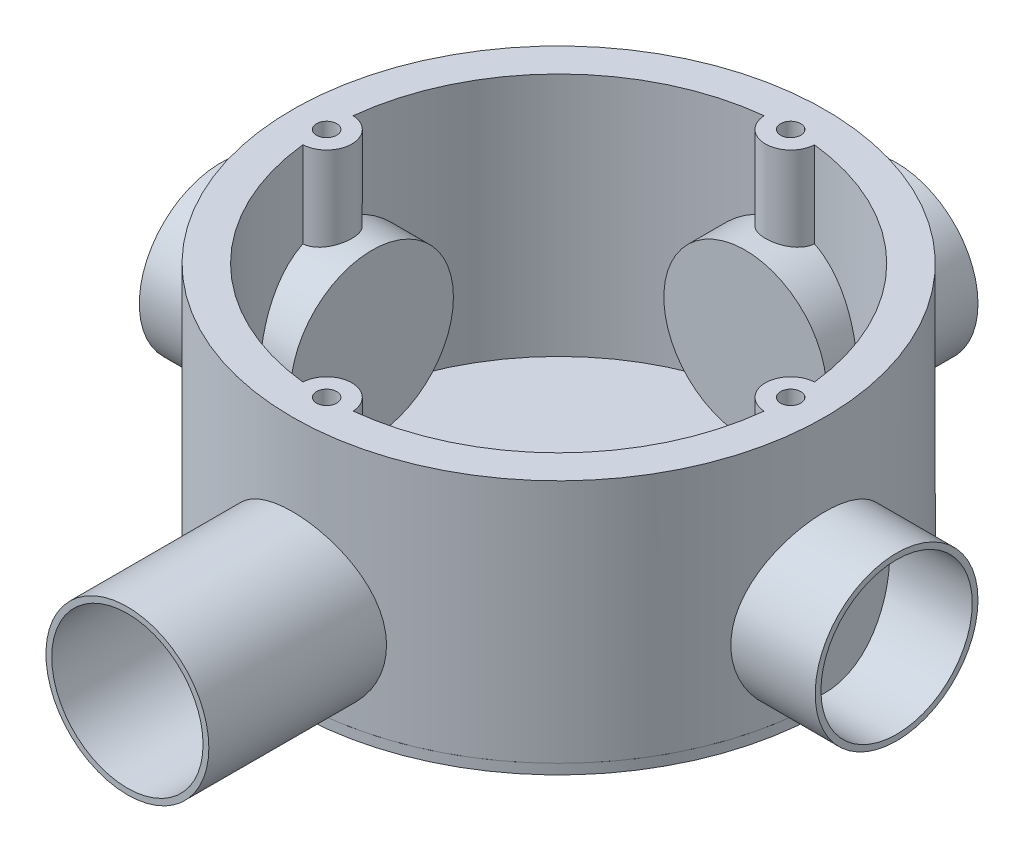
SolidWorks part; units mm, degrees
ref_plane "Plan de face" through (0, 0, 0) normal (0, 0, 1) x (1, 0, 0)
ref_plane "Plan de dessus" through (0, 0, 0) normal (0, 1, 0) x (1, 0, 0)
ref_plane "Plan de droite" through (0, 0, 0) normal (1, 0, 0) x (0, 0, -1)
sketch "Esquisse1" plane through (0, 0, 0) normal (0, 1, 0) x (1, 0, 0)
  line L0 (0, 0) -> (0, 52.8) construction
  line L1 (0, 52.8) -> (0, -52.8) construction
  line L2 (0, -52.8) -> (52.8, 0) construction
  line L3 (52.8, 0) -> (-52.8, 0) construction
  line L4 (0, 46) -> (0, 52.8) construction
  line L5 (0, 46) -> (0, 49.4) construction
  arc A0 (-45.7283, -4.9926) -> (-4.9926, -45.7283) centre (0, 0) ccw
  circle A1 centre (0, 0) radius 52.8
  arc A2 (-4.9926, 45.7283) -> (4.9926, 45.7283) centre (0, 46) ccw
  arc A4 (4.9926, -45.7283) -> (-4.9926, -45.7283) centre (0, -46) ccw
  arc A5 (-45.7283, -4.9926) -> (-45.7283, 4.9926) centre (-46, 0) ccw
  circle A6 centre (46, 0) radius 2
  circle A7 centre (0, -46) radius 2
  circle A8 centre (-46, 0) radius 2
  circle A9 centre (0, 46) radius 2
  arc A10 (4.9926, -45.7283) -> (45.7283, -4.9926) centre (0, 0) ccw
  arc A11 (45.7283, 4.9926) -> (4.9926, 45.7283) centre (0, 0) ccw
  arc A12 (45.7283, 4.9926) -> (45.7283, -4.9926) centre (46, 0) ccw
  arc A13 (-4.9926, 45.7283) -> (-45.7283, 4.9926) centre (0, 0) ccw
extrude "Boss.-Extru.1" add sketch "Esquisse1" along normal blind 48.5
sketch "Esquisse2" plane through (0, 0, 0) normal (0, 0, 1) x (1, 0, 0)
  line L0 (0, 48.5) -> (0, 0) construction
  line L1 (52.8, 48.5) -> (-52.8, 48.5) construction
  line L2 (0, 0) -> (0, 16.15) construction
  line L3 (-44, 48.5) -> (-48, 48.5) construction
  circle A0 centre (0, 16.15) radius 16.15
  circle A1 centre (0, 16.15) radius 15
sketch "Esquisse3" plane through (0, 48.5, 0) normal (0, 1, 0) x (1, 0, 0)
  line L0 (0, -46) -> (0, -37) construction
  line L1 (0, -37) -> (-8.1337, -37) construction
ref_plane "Plan1" through (0, 0, 37) normal (0, 0, 1) x (1, 0, 0)
extrude "Boss.-Extru.2" add sketch "Esquisse2" along normal blind 48.5 from surface starting at plane "Plan1"
sketch "Esquisse4" plane through (0, 0, 37) normal (0, 0, -1) x (-1, 0, 0)
  circle A0 centre (0, 16.15) radius 16.15
extrude "Boss.-Extru.3" add sketch "Esquisse4" against normal blind 3
sketch "Esquisse5" plane through (0, 48.5, 0) normal (0, 1, 0) x (1, 0, 0)
  line L0 (46, 0) -> (37, 0) construction
  line L1 (0, 46) -> (0, 37) construction
  line L2 (0, 37) -> (-46, 0) construction
  line L3 (-46, 0) -> (-37, 0) construction
ref_plane "Plan2" through (0, 0, -37) normal (0, 0, 1) x (1, 0, 0)
ref_plane "Plan3" through (-37, 0, 0) normal (1, 0, 0) x (0, 0, -1)
ref_plane "Plan4" through (37, 0, 0) normal (1, 0, 0) x (0, 0, -1)
sketch "Esquisse6" plane through (-37, 0, 0) normal (1, 0, 0) x (0, 0, -1)
  line L0 (0, 0) -> (0, 16.14) construction
  circle A0 centre (0, 16.14) radius 16.14
  circle A1 centre (0, 16.14) radius 15
extrude "Boss.-Extru.4" add sketch "Esquisse6" against normal blind 30
sketch "Esquisse7" plane through (-37, 0, 0) normal (1, 0, 0) x (0, 0, -1)
  circle A0 centre (0, 16.14) radius 16.14
extrude "Boss.-Extru.5" add sketch "Esquisse7" against normal blind 3
sketch "Esquisse8" plane through (0, 0, -37) normal (0, 0, 1) x (1, 0, 0)
  line L0 (0, 0) -> (0, 16.14) construction
  circle A0 centre (0, 16.14) radius 16.14
  circle A1 centre (0, 16.14) radius 15
extrude "Boss.-Extru.6" add sketch "Esquisse8" against normal blind 30
sketch "Esquisse9" plane through (0, 0, -37) normal (0, 0, 1) x (1, 0, 0)
  circle A0 centre (0, 16.14) radius 16.14
extrude "Boss.-Extru.7" add sketch "Esquisse9" against normal blind 3
sketch "Esquisse10" plane through (37, 0, 0) normal (1, 0, 0) x (0, 0, -1)
  line L0 (0, 0) -> (0, 16.14) construction
  circle A0 centre (0, 16.14) radius 16.14
  circle A1 centre (0, 16.14) radius 15
extrude "Boss.-Extru.8" add sketch "Esquisse10" along normal blind 30
sketch "Esquisse11" plane through (37, 0, 0) normal (-1, 0, 0) x (0, 0, 1)
  circle A0 centre (0, 16.14) radius 16.14
extrude "Boss.-Extru.9" add sketch "Esquisse11" against normal blind 3
sketch "Esquisse12" plane through (0, 0, 0) normal (0, -1, 0) x (-1, 0, 0)
  circle A0 centre (0, 0) radius 52.8
extrude "Boss.-Extru.12" add sketch "Esquisse12" along normal blind 2 separate body
sketch "Esquisse13" plane through (0, 0, 0) normal (0, 1, 0) x (1, 0, 0)
  line L0 (16.14, 40.0378) -> (16.14, 31.0446) construction
  line L1 (16.14, 37) -> (16.14, 43.0755) construction
  line L2 (16.14, 31.0446) -> (16.14, 37) construction
  line L3 (-27.775, 37) -> (27.775, 37) construction
  line L4 (16.14, 37) -> (37, 16.14) construction
  line L5 (37, -27.775) -> (37, 27.775) construction
  circle A0 centre (26.57, 26.57) radius 6
  circle A1 centre (26.57, 26.57) radius 3.9541
extrude "Boss.-Extru.13" add sketch "Esquisse13" along normal blind 3.8
sketch "Esquisse14" plane through (0, 0, 0) normal (0, 1, 0) x (1, 0, 0)
  line L0 (-40.0378, -16.14) -> (-37, -16.14) construction
  line L1 (-43.0755, -16.14) -> (-37, -16.14) construction
  line L2 (-37, -27.775) -> (-37, 27.775) construction
  line L3 (-37, -16.14) -> (-16.15, -37) construction
  circle A0 centre (-26.575, -26.57) radius 6
  circle A1 centre (-26.575, -26.57) radius 3
extrude "Boss.-Extru.14" add sketch "Esquisse14" along normal blind 3.8
sketch "Esquisse15" plane through (0, 0, 0) normal (0, 1, 0) x (1, 0, 0)
  circle A0 centre (0, 0) radius 7.5
extrude "Boss.-Extru.15" add sketch "Esquisse15" along normal blind 3 contours A0
fillet "Congé1" radius 10 1 edges at (0, 3, 7.5)
